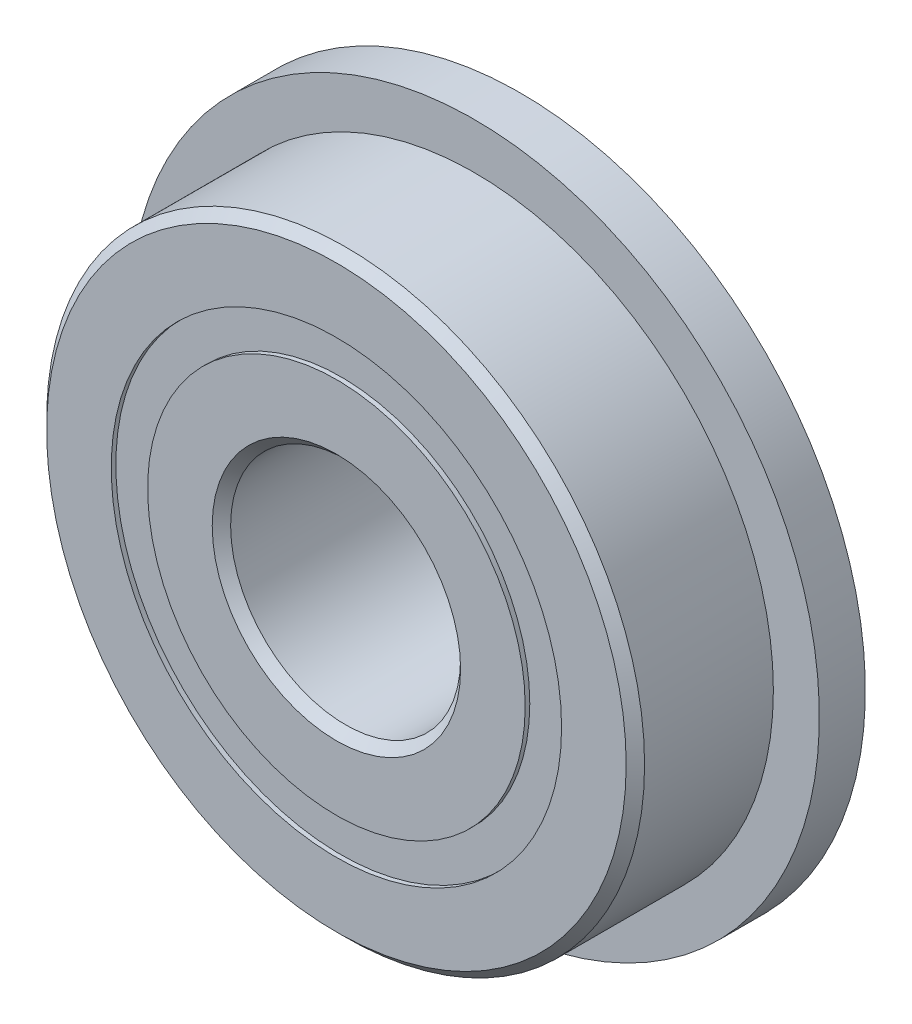
SolidWorks part; units mm, degrees
ref_plane "Front Plane" through (0, 0, 0) normal (0, 0, 1) x (1, 0, 0)
ref_plane "Top Plane" through (0, 0, 0) normal (0, 1, 0) x (1, 0, 0)
ref_plane "Right Plane" through (0, 0, 0) normal (1, 0, 0) x (0, 0, -1)
sketch "Sketch1" plane through (0, 0, 0) normal (1, 0, 0) x (0, 0, -1)
  line L0 (-2, 0) -> (2, 0) construction
  line L1 (0, 6.5) -> (0, -6.5) construction
  line L2 (1.8, 6.5) -> (-1.8, 6.5)
  line L3 (-1.8, 6.5) -> (-2, 6.3)
  line L4 (-2, 6.3) -> (-2, 4.8956)
  line L5 (-2, 4.8956) -> (-0.8889, 4.8956)
  line L6 (2, 4.8956) -> (0.8889, 4.8956)
  line L7 (2, 6.3) -> (2, 4.8956)
  line L8 (1.8, 6.5) -> (2, 6.3)
  line L9 (0, 6.5) -> (0, 4.5) construction
  line L10 (0, 4.5) -> (0, 2.5) construction
  arc A0 (-0.8889, 4.8956) -> (0.8889, 4.8956) centre (0, 4.5) cw
  point P14 (0, 2.5)
  dimension "D3" = 1.7778
  dimension "D1" = 45
  dimension "Width" = 4
  dimension "OD" = 13
  dimension "D2" = 0.2
  dimension "Shaft Dia" = 5
  dimension "D4" = 0.3956
revolve "Revolve1" add sketch "Sketch1" angle 360 about L0
sketch "Sketch3" plane through (0, 0, 0) normal (1, 0, 0) x (0, 0, -1)
  line L0 (-2, 4.1044) -> (-0.8889, 4.1044)
  line L1 (0, 6.5) -> (0, -6.5) construction
  line L2 (-2, 6.3) -> (-2, 4.8956) construction
  line L3 (-2, 4.1044) -> (-2, 2.7)
  line L4 (-1.8, 6.5) -> (-2, 6.3) construction
  line L5 (-2, 2.7) -> (-1.8, 2.5)
  line L6 (-1.8, 2.5) -> (1.8, 2.5)
  line L7 (1.8, 6.5) -> (1.8, -6.5) construction
  line L8 (1.8, 2.5) -> (2, 2.7)
  line L9 (2, -6.3) -> (2, 6.3) construction
  line L10 (2, 2.7) -> (2, 4.1044)
  line L11 (2, 4.1044) -> (0.8889, 4.1044)
  line L13 (1.8, 6.5) -> (2, 6.3) construction
  arc A0 (0.8889, 4.8956) -> (-0.8889, 4.8956) centre (0, 4.5) ccw construction
  arc A1 (0.8889, 4.1044) -> (-0.8889, 4.1044) centre (0, 4.5) cw
revolve "Revolve3" add sketch "Sketch3" angle 360 about L0
sketch "Sketch4" plane through (0, 0, 0) normal (1, 0, 0) x (0, 0, -1)
  line L0 (-0.9729, 4.5) -> (0.9729, 4.5)
  arc A2 (-0.9729, 4.5) -> (0.9729, 4.5) centre (0, 4.5) cw
  arc A3 (0.8889, 4.8956) -> (-0.8889, 4.8956) centre (0, 4.5) ccw construction
revolve "Revolve4" add sketch "Sketch4" angle 360 about L0
ref_axis "Axis1" through (0, 0, -2) along (0, 0, 1)
pattern_circular "CirPattern1" count 12 every 30 about axis through (0, 0, -2) along (0, 0, 1) of bodies 104
sketch "Sketch5" plane through (0, 0, 0) normal (1, 0, 0) x (0, 0, -1)
  line L0 (-2, 4.8956) -> (-0.8889, 4.8956) construction
  line L1 (-1.9, 4.8956) -> (-0.9729, 4.8956)
  line L2 (-1.9, 4.8956) -> (-1.9, 4.1044)
  line L3 (-1.9, 4.1044) -> (-0.9729, 4.1044)
  line L4 (-0.9729, 4.8956) -> (-0.9729, 4.1044)
  line L5 (-2, 4.1044) -> (-0.8889, 4.1044) construction
  line L6 (2, 4.8956) -> (0.8889, 4.8956) construction
  line L7 (1.9, 4.8956) -> (0.9729, 4.8956)
  line L8 (1.9, 4.8956) -> (1.9, 4.1044)
  line L9 (1.9, 4.1044) -> (0.9729, 4.1044)
  line L10 (0.9729, 4.8956) -> (0.9729, 4.1044)
  line L11 (2, 4.1044) -> (0.8889, 4.1044) construction
  line L12 (-1.8, 6.5) -> (-2, 6.3) construction
  point P18 (-1.9, 6.4)
revolve "Revolve5" add sketch "Sketch5" angle 360 about L0
sketch "Sketch6" plane through (0, 0, 0) normal (1, 0, 0) x (0, 0, -1)
  line L0 (2, 0) -> (-2, 0) construction
  line L1 (2, 4.8956) -> (1, 4.8956)
  line L2 (2, 4.8956) -> (2, 7.5)
  line L3 (2, 7.5) -> (1, 7.5)
  line L4 (1, 4.8956) -> (1, 7.5)
  dimension "Th" = 1
  dimension "Flange OD" = 15
revolve "Revolve6" add sketch "Sketch6" angle 360 about L0
equation "\"D2@Sketch1\" = \"Width@Sketch1\"*.05"
equation "\"D3@Sketch1\" = \"Width@Sketch1\"/2.25"
equation "\"D4@Sketch1\" = (((\"OD@Sketch1\"-\"Width@Sketch1\")/2)/3.25)/3.5"
equation "\"D2@CirPattern1\" = 360/\"Balls@CirPattern1\""
